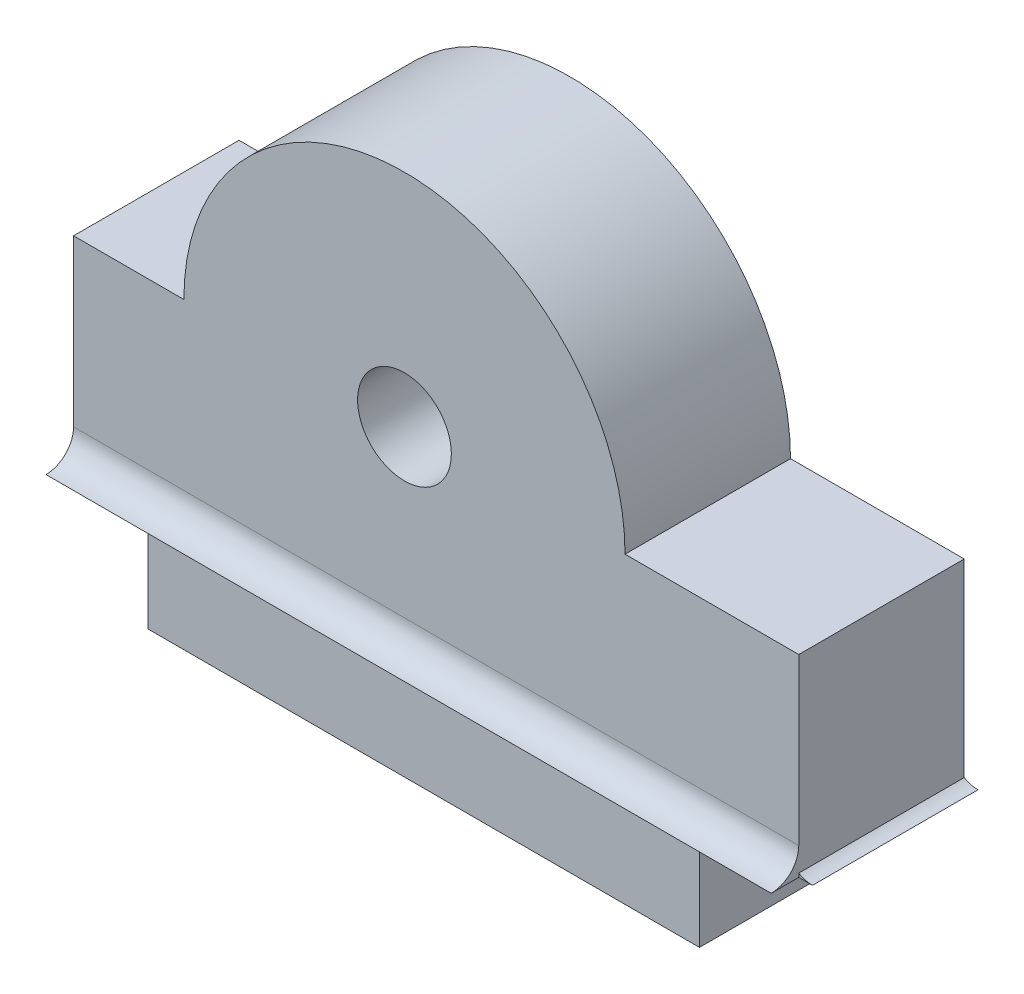
SolidWorks part; units mm, degrees
ref_plane "Front Plane" through (0, 0, 0) normal (0, 0, 1) x (1, 0, 0)
ref_plane "Top Plane" through (0, 0, 0) normal (0, 1, 0) x (1, 0, 0)
ref_plane "Right Plane" through (0, 0, 0) normal (1, 0, 0) x (0, 0, -1)
sketch "Sketch1" plane through (0, 0, 0) normal (0, 0, 1) x (1, 0, 0)
  line L0 (0, 0) -> (20, 0)
  line L1 (0, 0) -> (0, 4)
  line L2 (20, 0) -> (20, 4)
  line L3 (0, 4) -> (-2.7, 4)
  line L4 (23.6, 11) -> (23.6, 4)
  line L5 (-2.7, 4) -> (-2.7, 11)
  line L6 (-2.7, 11) -> (1.3, 11)
  line L7 (17.3, 11) -> (23.6, 11)
  line L8 (23.6, 4) -> (20, 4)
  line L11 (11.1187, 14.15) -> (7.4813, 14.15)
  line L12 (7.4813, 14.15) -> (5.6627, 11)
  line L13 (5.6627, 11) -> (7.4813, 7.85)
  line L14 (7.4813, 7.85) -> (11.1187, 7.85)
  line L15 (11.1187, 7.85) -> (12.9373, 11)
  line L16 (12.9373, 11) -> (11.1187, 14.15)
  arc A0 (17.3, 11) -> (1.3, 11) centre (9.3, 11) ccw
  circle A1 centre (9.3, 10.95) radius 3.2 construction
  point P19 (10, 0)
  dimension "D4" = 6.4
  dimension "D6" = 20
  dimension "D9" = 4
  dimension "D5" = 23.6
  dimension "D7" = 2.7
  dimension "D2" = 7
extrude "Boss-Extrude1" add sketch "Sketch1" along normal blind 6
sketch "Sketch2" plane through (-2.7, 0, 0) normal (-1, 0, 0) x (0, 0, 1)
  line L0 (3, 0) -> (3, 7) construction
  line L1 (6, 4) -> (6, 5)
  line L2 (6, 4) -> (7, 4)
  line L3 (0, 4) -> (-1, 4) construction
  line L4 (0, 4) -> (0, 5) construction
  arc A0 (6, 5) -> (7, 4) centre (7, 5) ccw
  arc A1 (0, 5) -> (-1, 4) centre (-1, 5) cw construction
  dimension "D1" = 1
  dimension "D2" = 1
  dimension "D3" = 6
  dimension "D4" = 3
  dimension "D5" = 4
extrude "Boss-Extrude2" add sketch "Sketch2" against normal up to surface (26.3 mm away) up to face at (23.6, 7.5, 3)
sketch "Sketch4" plane through (0, 0, 6) normal (0, 0, 1) x (1, 0, 0)
  line L0 (10.8, 0) -> (10.8, 7) construction
  line L1 (23.1, 4) -> (23.1, 5)
  line L2 (23.1, 4) -> (24.1, 4)
  line L3 (-1.5, 4) -> (-2.5, 4)
  line L4 (-1.5, 4) -> (-1.5, 5)
  arc A0 (23.1, 5) -> (24.1, 4) centre (24.1, 5) ccw
  arc A1 (-1.5, 5) -> (-2.5, 4) centre (-2.5, 5) cw
  dimension "D1" = 1
  dimension "D2" = 1
  dimension "D3" = 10.8
  dimension "D4" = 12.3
  dimension "D5" = 4
extrude "Boss-Extrude3" add sketch "Sketch4" against normal up to surface (6 mm away) up to face at (10.04, 6.8, 0)
sketch "Sketch8" plane through (0, 0, 6) normal (0, 0, 1) x (1, 0, 0)
  line L0 (5.6627, 11) -> (12.9373, 11) construction
  line L1 (11.1187, 14.15) -> (7.4813, 14.15) construction
  line L4 (7.4525, 14.2) -> (5.605, 11)
  line L5 (5.605, 11) -> (7.4525, 7.8)
  line L6 (7.4525, 7.8) -> (11.1475, 7.8)
  line L7 (11.1475, 7.8) -> (12.995, 11)
  line L8 (12.995, 11) -> (11.1475, 14.2)
  line L9 (11.1475, 14.2) -> (7.4525, 14.2)
  circle A0 centre (9.3, 11) radius 3.2 construction
  circle A1 centre (9.3, 11) radius 1.7
  point P4 (9.3, 11)
  point P6 (9.3, 7.8)
  point P14 (9.3, 14.15)
  dimension "D1" = 6.4
  dimension "D2" = 3.4
extrude "Boss-Extrude4" add sketch "Sketch8" against normal blind 3
equation "\"D4@Sketch1\" = 6 + \"tol1@parametersSketch@prostheticParameters.SLDPRT\""
equation "\"D1@Sketch8\"= 6 + \"tol1@parametersSketch@prostheticParameters.SLDPRT\""
equation "\"D2@Sketch8\"= 3 + \"tol1@parametersSketch@prostheticParameters.SLDPRT\""
